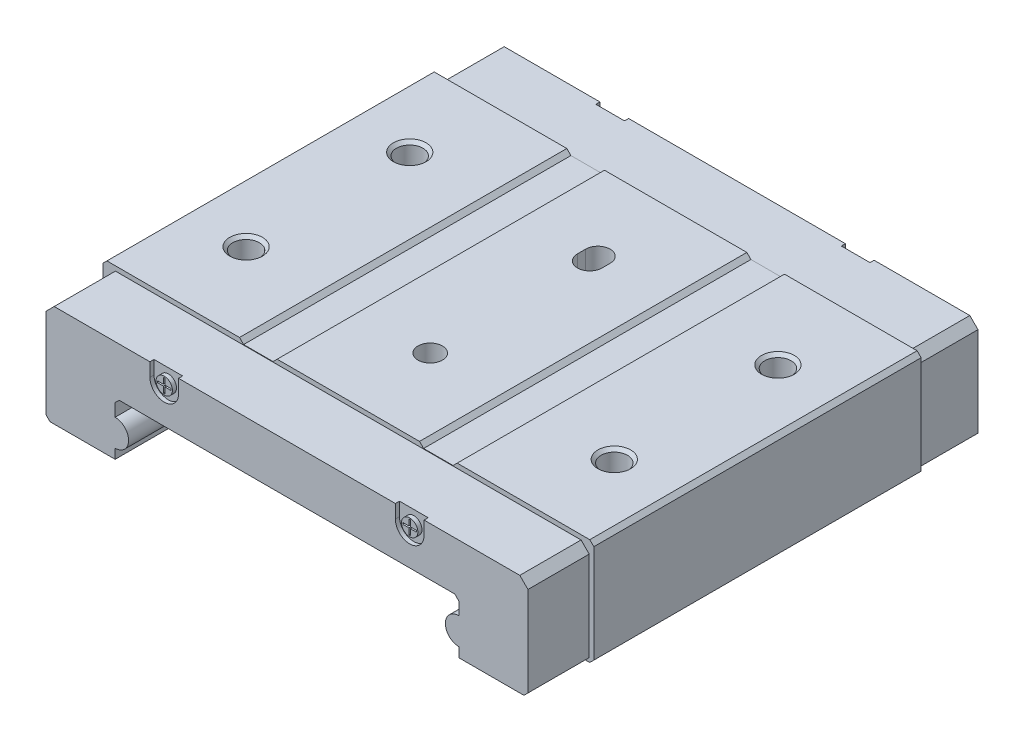
SolidWorks part; units mm, degrees
material "Plain Carbon Steel"
ref_plane "Front Plane" through (0, 0, 0) normal (0, 0, 1) x (1, 0, 0)
ref_plane "Top Plane" through (0, 0, 0) normal (0, 1, 0) x (1, 0, 0)
ref_plane "Right Plane" through (0, 0, 0) normal (1, 0, 0) x (0, 0, -1)
ref_plane "Plane1" through (0, 0, 0) normal (0, 0, 1) x (1, 0, 0)
sketch "Sketch1" plane through (0, 0, 0) normal (0, 0, 1) x (1, 0, 0)
  line L0 (-30, 12.505) -> (-30, 0.495)
  line L1 (-30, 0.495) -> (-28.9711, -0.5339)
  line L2 (-28.9711, -0.5339) -> (-21, -0.5339)
  line L3 (-21, -0.5339) -> (-21, 1.176)
  line L4 (-21, 4.456) -> (-21, 6.005)
  line L5 (-21, 6.005) -> (-20.505, 6.5)
  line L6 (-20.505, 6.5) -> (20.505, 6.5)
  line L7 (20.505, 6.5) -> (21, 6.005)
  line L8 (21, 6.005) -> (21, 4.456)
  line L9 (21, 1.176) -> (21, 0)
  line L10 (21, 0) -> (29.505, 0)
  line L11 (29.505, 0) -> (30, 0.495)
  line L12 (30, 0.495) -> (30, 12.505)
  line L13 (30, 12.505) -> (29.505, 13)
  line L14 (29.505, 13) -> (13.3, 13)
  line L15 (13.3, 13) -> (12.8, 12.5)
  line L16 (12.8, 12.5) -> (9.2, 12.5)
  line L17 (9.2, 12.5) -> (8.7, 13)
  line L18 (8.7, 13) -> (-8.7, 13)
  line L19 (-8.7, 13) -> (-9.2, 12.5)
  line L20 (-9.2, 12.5) -> (-12.8, 12.5)
  line L21 (-12.8, 12.5) -> (-13.3, 13)
  line L22 (-13.3, 13) -> (-29.505, 13)
  line L23 (-29.505, 13) -> (-30, 12.505)
  arc A0 (-21, 1.176) -> (-21, 4.456) centre (-21, 2.816) ccw
  arc A1 (21, 4.456) -> (21, 1.176) centre (21, 2.816) ccw
extrude "Boss-Extrude1" add sketch "Sketch1" against normal blind 20 and the other way blind 20
ref_plane "Plane2" through (0, 0, 20) normal (0, 0, 1) x (1, 0, 0)
sketch "Sketch2" plane through (0, 0, 20) normal (0, 0, 1) x (1, 0, 0)
  line L0 (-29.45, 11.453) -> (-29.45, 0.495)
  line L1 (-29.45, 0.495) -> (-28.955, 0)
  line L2 (-28.955, 0) -> (-21, 0)
  line L3 (-21, 0) -> (-21, 1.176)
  line L4 (-21, 4.456) -> (-21, 6.005)
  line L5 (-21, 6.005) -> (-20.505, 6.5)
  line L6 (-20.505, 6.5) -> (20.505, 6.5)
  line L7 (20.505, 6.5) -> (21, 6.005)
  line L8 (21, 6.005) -> (21, 4.456)
  line L9 (21, 1.176) -> (21, 0)
  line L10 (21, 0) -> (28.955, 0)
  line L11 (28.955, 0) -> (29.45, 0.495)
  line L12 (29.45, 0.495) -> (29.45, 11.453)
  line L13 (29.45, 11.453) -> (28.453, 12.45)
  line L14 (28.453, 12.45) -> (-28.453, 12.45)
  line L15 (-28.453, 12.45) -> (-29.45, 11.453)
  arc A0 (-21, 1.176) -> (-21, 4.456) centre (-21, 2.816) ccw
  arc A1 (21, 4.456) -> (21, 1.176) centre (21, 2.816) ccw
extrude "Boss-Extrude2" add sketch "Sketch2" against normal blind 7.5 and the other way blind 7.5
ref_plane "Plane3" through (0, 0, 20) normal (0, 0, 1) x (1, 0, 0)
sketch "Sketch3" plane through (0, 0, 20) normal (0, 0, 1) x (1, 0, 0)
  line L0 (-40, 40) -> (-40, -40)
  line L1 (-40, -40) -> (40, -40)
  line L2 (40, -40) -> (40, 40)
  line L3 (40, 40) -> (-40, 40)
  line L4 (-29.44, 11.443) -> (-29.44, 0.505)
  line L5 (-29.44, 0.505) -> (-28.945, 0.01)
  line L6 (-28.945, 0.01) -> (-21.01, 0.01)
  line L7 (-21.01, 0.01) -> (-21.01, 1.206)
  line L8 (-21.01, 4.446) -> (-21.01, 6.51)
  line L9 (-21.01, 6.51) -> (21.01, 6.51)
  line L10 (21.01, 6.51) -> (21.01, 4.446)
  line L11 (21.01, 1.206) -> (21.01, 0.01)
  line L12 (21.01, 0.01) -> (28.945, 0.01)
  line L13 (28.945, 0.01) -> (29.44, 0.505)
  line L14 (29.44, 0.505) -> (29.44, 11.443)
  line L15 (29.44, 11.443) -> (28.443, 12.44)
  line L16 (28.443, 12.44) -> (-28.443, 12.44)
  line L17 (-28.443, 12.44) -> (-29.44, 11.443)
  arc A0 (-21.01, 1.206) -> (-21.01, 4.446) centre (-21.01, 2.826) ccw
  arc A1 (21.01, 4.446) -> (21.01, 1.206) centre (21.01, 2.826) ccw
extrude "Cut-Extrude1" cut sketch "Sketch3" along normal blind 0.02
ref_plane "Plane4" through (0, 0, -20) normal (0, 0, 1) x (1, 0, 0)
sketch "Sketch4" plane through (0, 0, -20) normal (0, 0, 1) x (1, 0, 0)
  line L0 (-29.45, 11.453) -> (-29.45, 0.495)
  line L1 (-29.45, 0.495) -> (-28.955, 0)
  line L2 (-28.955, 0) -> (-21, 0)
  line L3 (-21, 0) -> (-21, 1.176)
  line L4 (-21, 4.456) -> (-21, 6.005)
  line L5 (-21, 6.005) -> (-20.505, 6.5)
  line L6 (-20.505, 6.5) -> (20.505, 6.5)
  line L7 (20.505, 6.5) -> (21, 6.005)
  line L8 (21, 6.005) -> (21, 4.456)
  line L9 (21, 1.176) -> (21, 0)
  line L10 (21, 0) -> (28.955, 0)
  line L11 (28.955, 0) -> (29.45, 0.495)
  line L12 (29.45, 0.495) -> (29.45, 11.453)
  line L13 (29.45, 11.453) -> (28.453, 12.45)
  line L14 (28.453, 12.45) -> (-28.453, 12.45)
  line L15 (-28.453, 12.45) -> (-29.45, 11.453)
  arc A0 (-21, 1.176) -> (-21, 4.456) centre (-21, 2.816) ccw
  arc A1 (21, 4.456) -> (21, 1.176) centre (21, 2.816) ccw
extrude "Boss-Extrude3" add sketch "Sketch4" against normal blind 7.5 and the other way blind 7.5
ref_plane "Plane5" through (0, 0, -20) normal (0, 0, 1) x (1, 0, 0)
sketch "Sketch5" plane through (0, 0, -20) normal (0, 0, 1) x (1, 0, 0)
  line L0 (-40, 40) -> (-40, -40)
  line L1 (-40, -40) -> (40, -40)
  line L2 (40, -40) -> (40, 40)
  line L3 (40, 40) -> (-40, 40)
  line L4 (-29.44, 11.443) -> (-29.44, 0.505)
  line L5 (-29.44, 0.505) -> (-28.945, 0.01)
  line L6 (-28.945, 0.01) -> (-21.01, 0.01)
  line L7 (-21.01, 0.01) -> (-21.01, 1.206)
  line L8 (-21.01, 4.446) -> (-21.01, 6.51)
  line L9 (-21.01, 6.51) -> (21.01, 6.51)
  line L10 (21.01, 6.51) -> (21.01, 4.446)
  line L11 (21.01, 1.206) -> (21.01, 0.01)
  line L12 (21.01, 0.01) -> (28.945, 0.01)
  line L13 (28.945, 0.01) -> (29.44, 0.505)
  line L14 (29.44, 0.505) -> (29.44, 11.443)
  line L15 (29.44, 11.443) -> (28.443, 12.44)
  line L16 (28.443, 12.44) -> (-28.443, 12.44)
  line L17 (-28.443, 12.44) -> (-29.44, 11.443)
  arc A0 (-21.01, 1.206) -> (-21.01, 4.446) centre (-21.01, 2.826) ccw
  arc A1 (21.01, 4.446) -> (21.01, 1.206) centre (21.01, 2.826) ccw
extrude "Cut-Extrude2" cut sketch "Sketch5" against normal blind 0.02
ref_plane "Plane6" through (0, 0, -27.5) normal (0, 0, 1) x (1, 0, 0)
sketch "Sketch6" plane through (0, 0, -27.5) normal (0, 0, 1) x (1, 0, 0)
  line L0 (-16.75, 32) -> (-16.75, 10.8)
  line L1 (-13.25, 10.8) -> (-13.25, 30.825)
  line L2 (-13.25, 30.825) -> (13.25, 30.825)
  line L3 (13.25, 30.825) -> (13.25, 10.8)
  line L4 (16.75, 10.8) -> (16.75, 32)
  line L5 (16.75, 32) -> (-16.75, 32)
  arc A0 (-16.75, 10.8) -> (-13.25, 10.8) centre (-15, 10.8) ccw
  arc A1 (13.25, 10.8) -> (16.75, 10.8) centre (15, 10.8) ccw
extrude "Cut-Extrude3" cut sketch "Sketch6" against normal blind 0.5 and the other way blind 0.5
ref_plane "Plane7" through (0, 0, 27.5) normal (0, 0, 1) x (1, 0, 0)
sketch "Sketch7" plane through (0, 0, 27.5) normal (0, 0, 1) x (1, 0, 0)
  line L0 (-16.75, 32) -> (-16.75, 10.8)
  line L1 (-13.25, 10.8) -> (-13.25, 30.825)
  line L2 (-13.25, 30.825) -> (13.25, 30.825)
  line L3 (13.25, 30.825) -> (13.25, 10.8)
  line L4 (16.75, 10.8) -> (16.75, 32)
  line L5 (16.75, 32) -> (-16.75, 32)
  arc A0 (-16.75, 10.8) -> (-13.25, 10.8) centre (-15, 10.8) ccw
  arc A1 (13.25, 10.8) -> (16.75, 10.8) centre (15, 10.8) ccw
extrude "Cut-Extrude4" cut sketch "Sketch7" against normal blind 0.5
ref_plane "Plane8" through (0, 0, -27.5) normal (0, 0, 1) x (1, 0, 0)
sketch "Sketch8" plane through (0, 0, -27.5) normal (0, 0, 1) x (1, 0, 0)
  line L0 (-15.85, 10.9) -> (-15.85, 10.7)
  line L1 (-15.85, 10.7) -> (-15.1, 10.7)
  line L2 (-15.1, 10.7) -> (-15.1, 9.95)
  line L3 (-15.1, 9.95) -> (-14.9, 9.95)
  line L4 (-14.9, 9.95) -> (-14.9, 10.7)
  line L5 (-14.9, 10.7) -> (-14.15, 10.7)
  line L6 (-14.15, 10.7) -> (-14.15, 10.9)
  line L7 (-14.15, 10.9) -> (-14.9, 10.9)
  line L8 (-14.9, 10.9) -> (-14.9, 11.65)
  line L9 (-14.9, 11.65) -> (-15.1, 11.65)
  line L10 (-15.1, 11.65) -> (-15.1, 10.9)
  line L11 (-15.1, 10.9) -> (-15.85, 10.9)
  circle A0 centre (-15, 10.8) radius 1
extrude "Boss-Extrude4" add sketch "Sketch8" along normal blind 0.5
ref_plane "Plane9" through (0, 0, -27.5) normal (0, 0, 1) x (1, 0, 0)
sketch "Sketch9" plane through (0, 0, -27.5) normal (0, 0, 1) x (1, 0, 0)
  line L0 (14.15, 10.9) -> (14.15, 10.7)
  line L1 (14.15, 10.7) -> (14.9, 10.7)
  line L2 (14.9, 10.7) -> (14.9, 9.95)
  line L3 (14.9, 9.95) -> (15.1, 9.95)
  line L4 (15.1, 9.95) -> (15.1, 10.7)
  line L5 (15.1, 10.7) -> (15.85, 10.7)
  line L6 (15.85, 10.7) -> (15.85, 10.9)
  line L7 (15.85, 10.9) -> (15.1, 10.9)
  line L8 (15.1, 10.9) -> (15.1, 11.65)
  line L9 (15.1, 11.65) -> (14.9, 11.65)
  line L10 (14.9, 11.65) -> (14.9, 10.9)
  line L11 (14.9, 10.9) -> (14.15, 10.9)
  circle A0 centre (15, 10.8) radius 1
extrude "Boss-Extrude5" add sketch "Sketch9" along normal blind 0.5
ref_plane "Plane10" through (0, 0, 27.5) normal (0, 0, 1) x (1, 0, 0)
sketch "Sketch10" plane through (0, 0, 27.5) normal (0, 0, 1) x (1, 0, 0)
  line L0 (-15.85, 10.9) -> (-15.85, 10.7)
  line L1 (-15.85, 10.7) -> (-15.1, 10.7)
  line L2 (-15.1, 10.7) -> (-15.1, 9.95)
  line L3 (-15.1, 9.95) -> (-14.9, 9.95)
  line L4 (-14.9, 9.95) -> (-14.9, 10.7)
  line L5 (-14.9, 10.7) -> (-14.15, 10.7)
  line L6 (-14.15, 10.7) -> (-14.15, 10.9)
  line L7 (-14.15, 10.9) -> (-14.9, 10.9)
  line L8 (-14.9, 10.9) -> (-14.9, 11.65)
  line L9 (-14.9, 11.65) -> (-15.1, 11.65)
  line L10 (-15.1, 11.65) -> (-15.1, 10.9)
  line L11 (-15.1, 10.9) -> (-15.85, 10.9)
  circle A0 centre (-15, 10.8) radius 1
extrude "Boss-Extrude6" add sketch "Sketch10" against normal blind 0.5
ref_plane "Plane11" through (0, 0, 27.5) normal (0, 0, 1) x (1, 0, 0)
sketch "Sketch11" plane through (0, 0, 27.5) normal (0, 0, 1) x (1, 0, 0)
  line L0 (14.15, 10.9) -> (14.15, 10.7)
  line L1 (14.15, 10.7) -> (14.9, 10.7)
  line L2 (14.9, 10.7) -> (14.9, 9.95)
  line L3 (14.9, 9.95) -> (15.1, 9.95)
  line L4 (15.1, 9.95) -> (15.1, 10.7)
  line L5 (15.1, 10.7) -> (15.85, 10.7)
  line L6 (15.85, 10.7) -> (15.85, 10.9)
  line L7 (15.85, 10.9) -> (15.1, 10.9)
  line L8 (15.1, 10.9) -> (15.1, 11.65)
  line L9 (15.1, 11.65) -> (14.9, 11.65)
  line L10 (14.9, 11.65) -> (14.9, 10.9)
  line L11 (14.9, 10.9) -> (14.15, 10.9)
  circle A0 centre (15, 10.8) radius 1
extrude "Boss-Extrude7" add sketch "Sketch11" against normal blind 0.5
ref_plane "Plane12" through (22.5, 0, 0) normal (1, 0, 0) x (0, 0, -1)
sketch "Sketch12" plane through (22.5, 0, 0) normal (1, 0, 0) x (0, 0, -1)
  line L0 (-10, 13) -> (-8, 13)
  line L1 (-8, 13) -> (-8.379, 12.621)
  line L2 (-8.379, 12.621) -> (-8.379, 7.1859)
  line L3 (-8.379, 7.1859) -> (-10, 6.25)
  line L4 (-10, 6.25) -> (-10, 13)
  line L5 (-10, 6.25) -> (-10, 13) construction
revolve "Cut-Revolve1" cut sketch "Sketch12" angle 360 about L5 reverse direction yes
ref_plane "Plane13" through (-22.5, 0, 0) normal (1, 0, 0) x (0, 0, -1)
sketch "Sketch13" plane through (-22.5, 0, 0) normal (1, 0, 0) x (0, 0, -1)
  line L0 (10, 13) -> (12, 13)
  line L1 (12, 13) -> (11.621, 12.621)
  line L2 (11.621, 12.621) -> (11.621, 7.1859)
  line L3 (11.621, 7.1859) -> (10, 6.25)
  line L4 (10, 6.25) -> (10, 13)
  line L5 (10, 6.25) -> (10, 13) construction
revolve "Cut-Revolve2" cut sketch "Sketch13" angle 360 about L5 reverse direction yes
ref_plane "Plane14" through (22.5, 0, 0) normal (1, 0, 0) x (0, 0, -1)
sketch "Sketch14" plane through (22.5, 0, 0) normal (1, 0, 0) x (0, 0, -1)
  line L0 (10, 13) -> (12, 13)
  line L1 (12, 13) -> (11.621, 12.621)
  line L2 (11.621, 12.621) -> (11.621, 7.1859)
  line L3 (11.621, 7.1859) -> (10, 6.25)
  line L4 (10, 6.25) -> (10, 13)
  line L5 (10, 6.25) -> (10, 13) construction
revolve "Cut-Revolve3" cut sketch "Sketch14" angle 360 about L5 reverse direction yes
ref_plane "Plane15" through (-22.5, 0, 0) normal (1, 0, 0) x (0, 0, -1)
sketch "Sketch15" plane through (-22.5, 0, 0) normal (1, 0, 0) x (0, 0, -1)
  line L0 (-10, 13) -> (-8, 13)
  line L1 (-8, 13) -> (-8.379, 12.621)
  line L2 (-8.379, 12.621) -> (-8.379, 7.1859)
  line L3 (-8.379, 7.1859) -> (-10, 6.25)
  line L4 (-10, 6.25) -> (-10, 13)
  line L5 (-10, 6.25) -> (-10, 13) construction
revolve "Cut-Revolve4" cut sketch "Sketch15" angle 360 about L5 reverse direction yes
ref_plane "Plane16" through (0, 0, 10) normal (0, 0, 1) x (1, 0, 0)
sketch "Sketch16" plane through (0, 0, 10) normal (0, 0, 1) x (1, 0, 0)
  line L0 (0, 13) -> (1.5, 13)
  line L1 (1.5, 13) -> (1.5, 9)
  line L2 (1.5, 9) -> (0, 9)
  line L3 (0, 9) -> (0, 13)
  line L4 (0, 9) -> (0, 13) construction
revolve "Cut-Revolve5" cut sketch "Sketch16" angle 360 about L4 reverse direction yes
ref_plane "Plane17" through (0, 13, 0) normal (0, 1, 0) x (-1, 0, 0)
sketch "Sketch17" plane through (0, 13, 0) normal (0, 1, 0) x (-1, 0, 0)
  line L0 (1.5, -10.5) -> (1.5, -9.5)
  line L1 (-1.5, -9.5) -> (-1.5, -10.5)
  arc A0 (1.5, -9.5) -> (-1.5, -9.5) centre (0, -9.5) ccw
  arc A1 (-1.5, -10.5) -> (1.5, -10.5) centre (0, -10.5) ccw
extrude "Cut-Extrude5" cut sketch "Sketch17" against normal blind 4
